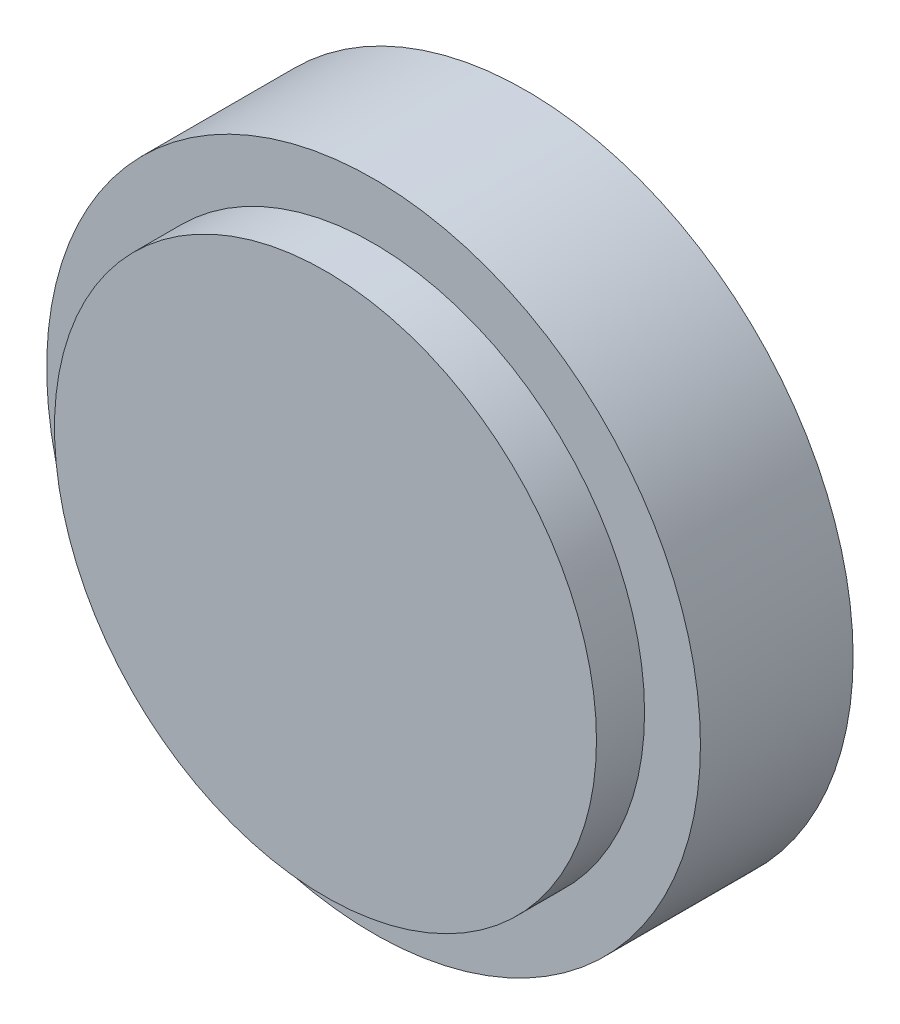
SolidWorks part; units mm, degrees
ref_plane "Alzado" through (0, 0, 0) normal (0, 0, 1) x (1, 0, 0)
ref_plane "Planta" through (0, 0, 0) normal (0, 1, 0) x (1, 0, 0)
ref_plane "Vista lateral" through (0, 0, 0) normal (1, 0, 0) x (0, 0, -1)
sketch "Croquis1" plane through (0, 0, 0) normal (0, 0, 1) x (1, 0, 0)
  circle A0 centre (0, 0) radius 42.82
  circle A1 centre (0, 0) radius 35.5
  dimension "D1" = 71
  dimension "D2" = 7.32
extrude "Saliente-Extruir2" add sketch "Croquis1" along normal blind 20 contours A1 | A0 A1 region at (-41.6089, 0, 0) region at (0, 0, 0)
extrude "Saliente-Extruir3" add sketch "Croquis1<3>" along normal blind 26.3 contours A1 region at (0, 0, 0)
sketch "Croquis1<3>" plane through (0, 0, 0) normal (0, 0, 1) x (1, 0, 0) same geometry as "Croquis1"
